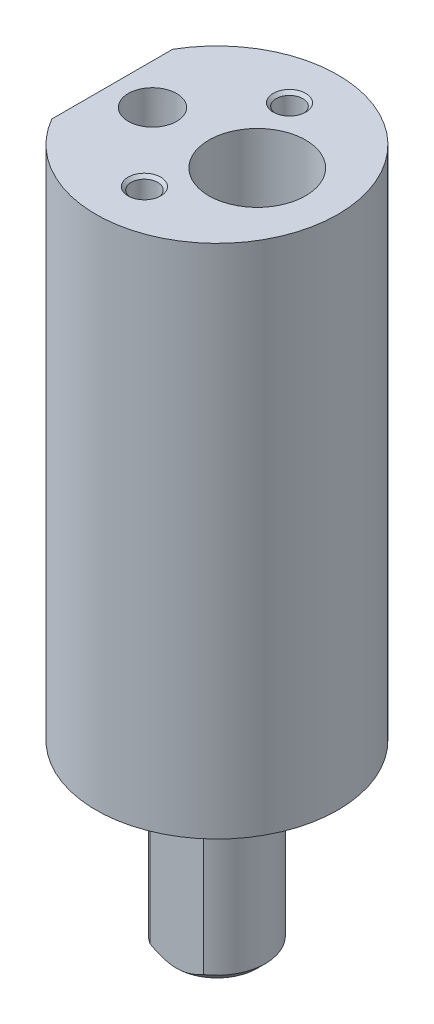
SolidWorks part; units mm, degrees
ref_plane "Front Plane" through (0, 0, 0) normal (0, 0, 1) x (1, 0, 0)
ref_plane "Top Plane" through (0, 0, 0) normal (0, 1, 0) x (1, 0, 0)
ref_plane "Right Plane" through (0, 0, 0) normal (1, 0, 0) x (0, 0, -1)
sketch "Sketch1" plane through (0, 0, 0) normal (0, 1, 0) x (1, 0, 0)
  line L0 (-3.3166, -5) -> (3.3166, -5)
  arc A0 (3.3166, -5) -> (-3.3166, -5) centre (0, 0) ccw
  dimension "D1" = 12
  dimension "D2" = 5
extrude "Boss-Extrude1" add sketch "Sketch1" along normal blind 22
sketch "Sketch2" plane through (0, 22, 0) normal (0, 1, 0) x (1, 0, 0)
  line L0 (-13, 7.4833) -> (-13, -7.4833)
  arc A0 (-13, -7.4833) -> (-13, 7.4833) centre (0, 0) ccw
  dimension "D1" = 30
  dimension "D2" = 13
extrude "Boss-Extrude2" add sketch "Sketch2" along normal blind 64
sketch "Sketch3" plane through (0, 86, 0) normal (0, 1, 0) x (1, 0, 0)
  line L0 (0, 0) -> (-13, 0) construction
  line L1 (-13, 7.4833) -> (-13, -7.4833) construction
  circle A0 centre (-8, 0) radius 3
  dimension "D2" = 6
  dimension "D1" = 8
extrude "Cut-Extrude1" cut sketch "Sketch3" against normal blind 65
sketch "Sketch4" plane through (0, 86, 0) normal (0, 1, 0) x (1, 0, 0)
  circle A0 centre (5, 0) radius 6
  point P2 (0, 0)
  dimension "D1" = 5
  dimension "D2" = 12
extrude "Cut-Extrude2" cut sketch "Sketch4" against normal blind 52
hole_wizard "M4 Tapped Hole1" positions "Sketch5" profile "Sketch6" tap size "M4" standard "ISO"
sketch "Sketch5" plane through (0, 86, 0) normal (0, 1, 0) x (1, 0, 0)
  line L0 (0, 9) -> (0, -9) construction
  point P1 (0, 9)
  point P2 (0, -9)
  dimension "D1" = 9
  dimension "D2" = 9
sketch "Sketch6" plane through (0, 86, -9) normal (1, 0, 0) x (0, 0, 1)
  line L0 (0, 0) -> (0, 14.9914)
  line L1 (0, 14.9914) -> (1.65, 14)
  line L2 (1.65, 14) -> (1.65, 0.375)
  line L3 (1.65, 0.375) -> (2.025, 0)
  line L5 (2.025, 0) -> (0, 0)
  line L6 (-1.65, 0.375) -> (-2.025, 0) construction
  line L10 (0, 14.9914) -> (-1.65, 14) construction
  line L11 (0, -6.35) -> (0, 107.95) construction
  dimension "Tap Drill Dia." = 3.3
  dimension "Tap Drill Depth" = 14
  dimension "Near C'Sink Dia." = 4.05
  dimension "Near C'Sink Angle" = 90
  dimension "Drill Angle" = 118
cosmetic thread "Hole Thread1" parameters "D1"=13.3, "D2"=4
cosmetic thread "Hole Thread2" parameters "D1"=13.3, "D2"=4
sketch "Sketch7" plane through (-13, 0, 0) normal (-1, 0, 0) x (0, 0, 1)
  line L0 (0, 86) -> (0, 22) construction
  line L1 (-7.4833, 86) -> (7.4833, 86) construction
  line L2 (-7.4833, 22) -> (7.4833, 22) construction
  circle A0 centre (0, 54) radius 2.5
  circle A1 centre (0, 25) radius 1.5
  dimension "D1" = 5
  dimension "D2" = 3
  dimension "D3" = 32
  dimension "D4" = 61
extrude "Cut-Extrude3" cut sketch "Sketch7" against normal blind 5
sketch "Sketch8" plane through (-13, 0, 0) normal (-1, 0, 0) x (0, 0, 1)
  line L0 (0, 86) -> (0, 22) construction
  line L1 (-7.4833, 86) -> (7.4833, 86) construction
  line L2 (-7.4833, 22) -> (7.4833, 22) construction
  circle A0 centre (0, 76) radius 1
  circle A1 centre (0, 34) radius 1
  dimension "D3" = 2
  dimension "D1" = 10
  dimension "D2" = 52
extrude "Cut-Extrude4" cut sketch "Sketch8" against normal blind 15
chamfer "Chamfer1" distance 1 angle 45 1 edges at (0, 0, -6)
